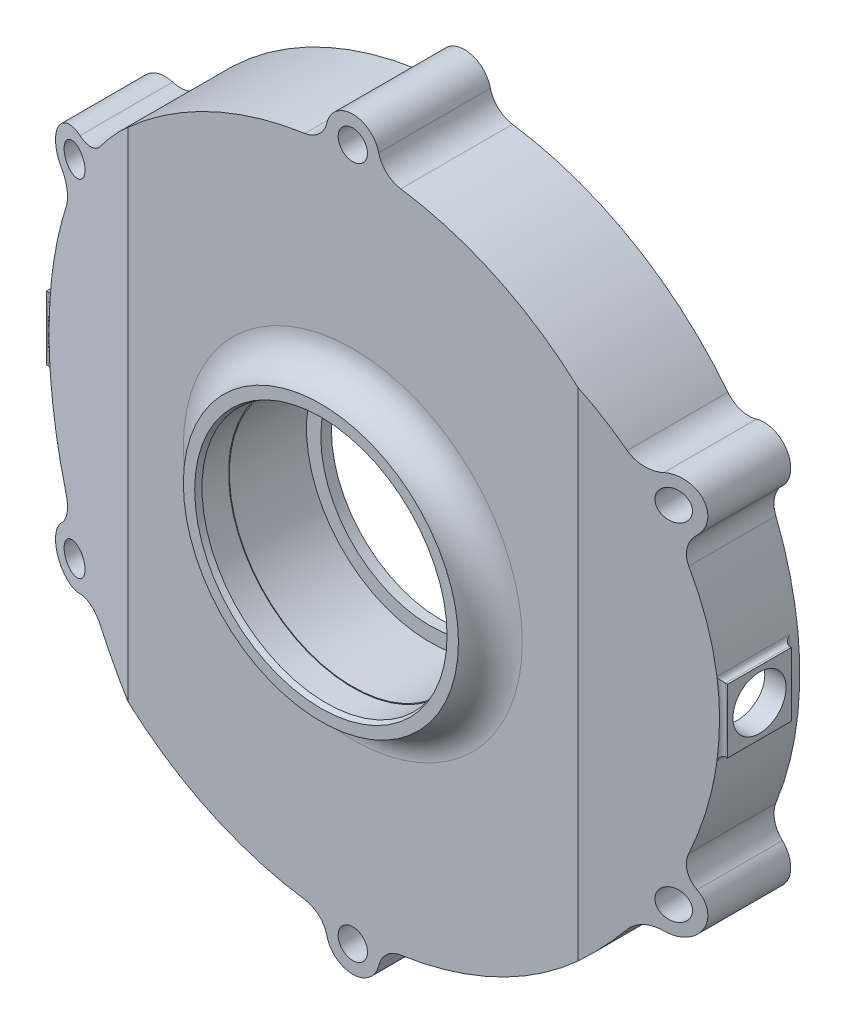
SolidWorks part; units mm, degrees
material "7075-T6 (SN)"
ref_plane "Front Plane" through (0, 0, 0) normal (0, 0, 1) x (1, 0, 0)
ref_plane "Top Plane" through (0, 0, 0) normal (0, 1, 0) x (1, 0, 0)
ref_plane "Right Plane" through (0, 0, 0) normal (1, 0, 0) x (0, 0, -1)
sketch "Sketch2" plane through (0, 0, 0) normal (1, 0, 0) x (0, 0, -1)
  line L0 (-66.5, 0) -> (66.5, 0) construction
  line L1 (0.1604, 63) -> (-20.8396, 63)
  line L3 (0.1604, 60) -> (-18.6396, 60)
  line L5 (0.1604, 63) -> (0.1604, 60)
  line L8 (-6.3396, 23.2) -> (-6.3396, 20.5148)
  line L11 (-6.3396, 20.5148) -> (-4.3396, 20.5148)
  line L14 (-18.8396, 59.8) -> (-18.8396, 27.5)
  line L21 (-20.8396, 23.2) -> (-6.3396, 23.2)
  line L22 (-20.8396, 23.2) -> (-20.8396, 63)
  line L25 (-4.3396, 27.136) -> (-4.3396, 20.5148)
  line L26 (-18.8396, 27.5) -> (-5.3396, 27.5)
  line L27 (-5.3396, 27.5) -> (-4.3396, 27.136)
  arc A0 (-18.6396, 60) -> (-18.8396, 59.8) centre (-18.6396, 59.8) ccw
  point P4 (0, 0)
  point P9 (-4.3396, 27.5)
  point P22 (-20.8396, 23.2)
  dimension "D8" = 0.2
  dimension "D12" = 20
  dimension "D4" = 1
  dimension "D2" = 27.5
  dimension "D3" = 3
  dimension "D5" = 21
  dimension "D6" = 2
  dimension "D7" = 14.5
  dimension "D9" = 2.6852
  dimension "D10" = 2
  dimension "D11" = 4.3
revolve "Revolve1" add sketch "Sketch2" angle 360 about L0
sketch "Sketch4" plane through (0, 0, -0.1604) normal (0, 0, -1) x (-1, 0, 0)
  line L0 (0, 0) -> (0, 65) construction
  circle A0 centre (0, 65) radius 5
  circle A2 centre (0, 65) radius 3
  dimension "D1" = 6
  dimension "D4" = 10
  dimension "D2" = 65
extrude "Boss-Extrude3" add sketch "Sketch4" along direction (0, 0, 1) on the side against the normal through all contours A0
sketch "Sketch11" plane through (0, 0, -0.1604) normal (0, 0, -1) x (-1, 0, 0)
  circle A0 centre (56.2917, 32.5) radius 2.75
  circle A1 centre (0, 65) radius 2.75
  circle A2 centre (56.2917, -32.5) radius 2.75
  circle A3 centre (0, -65) radius 2.75
  circle A4 centre (-56.2917, -32.5) radius 2.75
  circle A5 centre (-56.2917, 32.5) radius 2.75
  point P15 (0, 0)
  dimension "D1" = 5.5
  dimension "D2" = 65
  dimension "D3" = 6
fillet "Fillet2" radius 5 2 edges at (-4.5086, 62.8385, 10.3396) (4.5086, 62.8385, 10.3396)
pattern_circular "CirPattern2" count 6 over 360 about axis through (0, 0, -0.1604) along (0, 0, 1) of "Boss-Extrude3", "Fillet2"
chamfer "Chamfer1" distance 0.5 angle 45 1 edges at (60, 0, -0.1604)
sketch "Sketch20" plane through (0, 0, 0) normal (0, 1, 0) x (1, 0, 0)
  line L0 (-63, -12.8396) -> (-35, -20.8396)
  line L1 (-63, 0.1604) -> (-63, -20.8396) construction
  line L3 (-35, -20.8396) -> (-63, -20.8396)
  line L4 (-63, -20.8396) -> (-63, -12.8396)
  line L5 (0, -20.8396) -> (0, 8.0819) construction
  line L6 (-4.866, -20.8396) -> (4.866, -20.8396) construction
  line L7 (63, -20.8396) -> (63, -12.8396)
  line L8 (35, -20.8396) -> (63, -20.8396)
  line L9 (63, -12.8396) -> (35, -20.8396)
  dimension "D1" = 28
  dimension "D2" = 8
extrude "Cut-Extrude15" cut sketch "Sketch20" against normal blind 60 and the other way blind 60 contours L7 L9 L8 | L0 L3 L4 region at (53.6667, 0, 18.173)
sketch "Sketch21" plane through (0, 0, 0) normal (0, 1, 0) x (1, 0, 0)
  line L0 (-63, -12.8396) -> (-35, -20.8396)
  line L1 (-35, -20.8396) -> (-42.2801, -20.8396)
  line L2 (-42.2801, -20.8396) -> (-63, -14.9197)
  line L3 (-63, -12.8396) -> (-63, -14.9197)
  line L4 (0, -20.8396) -> (0, -12.247) construction
  line L5 (-4.866, -20.8396) -> (4.866, -20.8396) construction
  line L6 (63, -12.8396) -> (63, -14.9197)
  line L7 (42.2801, -20.8396) -> (63, -14.9197)
  line L8 (35, -20.8396) -> (42.2801, -20.8396)
  line L9 (63, -12.8396) -> (35, -20.8396)
  dimension "D1" = 2
extrude "Boss-Extrude8" add sketch "Sketch21" along normal blind 60 and the other way blind 60
sketch "Sketch22" plane through (0, 0, -0.1604) normal (0, 0, -1) x (-1, 0, 0)
  line L0 (35, 52.3832) -> (35, 60)
  line L3 (63, -60) -> (35, -60)
  line L4 (35, -60) -> (35, -52.3832)
  line L5 (63, 60) -> (35, 60)
  line L6 (63, -60) -> (63, 60)
  line L7 (-35, 52.3832) -> (-35, 60)
  line L8 (-35, 60) -> (-63, 60)
  line L9 (-63, 60) -> (-63, -60)
  line L10 (-63, -60) -> (-35, -60)
  line L11 (-35, -60) -> (-35, -52.3832)
  arc A24 (-9.0163, 62.3515) -> (-49.4898, 38.9841) centre (0, 0) ccw
  arc A25 (-54.8546, 37.289) -> (-49.4898, 38.9841) centre (-53.4176, 42.0781) ccw
  arc A26 (-54.8546, 37.289) -> (-59.7206, 28.861) centre (-56.2917, 32.5) ccw
  arc A27 (-58.5061, 23.3674) -> (-59.7206, 28.861) centre (-63.1495, 25.2219) ccw
  arc A28 (-58.5061, 23.3674) -> (-58.5061, -23.3674) centre (0, 0) ccw
  arc A29 (-59.7206, -28.861) -> (-58.5061, -23.3674) centre (-63.1495, -25.2219) ccw
  arc A30 (-59.7206, -28.861) -> (-54.8546, -37.289) centre (-56.2917, -32.5) ccw
  arc A31 (-49.4898, -38.9841) -> (-54.8546, -37.289) centre (-53.4176, -42.0781) ccw
  arc A32 (-49.4898, -38.9841) -> (-9.0163, -62.3515) centre (0, 0) ccw
  arc A33 (-4.866, -66.15) -> (-9.0163, -62.3515) centre (-9.7319, -67.3) ccw
  arc A34 (-4.866, -66.15) -> (4.866, -66.15) centre (0, -65) ccw
  arc A35 (9.0163, -62.3515) -> (4.866, -66.15) centre (9.7319, -67.3) ccw
  arc A36 (9.0163, -62.3515) -> (49.4898, -38.9841) centre (0, 0) ccw
  arc A44 (54.8546, -37.289) -> (49.4898, -38.9841) centre (53.4176, -42.0781) ccw
  arc A45 (54.8546, -37.289) -> (59.7206, -28.861) centre (56.2917, -32.5) ccw
  arc A46 (58.5061, -23.3674) -> (59.7206, -28.861) centre (63.1495, -25.2219) ccw
  arc A47 (58.5061, -23.3674) -> (58.5061, 23.3674) centre (0, 0) ccw
  arc A69 (59.7206, 28.861) -> (58.5061, 23.3674) centre (63.1495, 25.2219) ccw
  arc A70 (59.7206, 28.861) -> (54.8546, 37.289) centre (56.2917, 32.5) ccw
  arc A71 (49.4898, 38.9841) -> (54.8546, 37.289) centre (53.4176, 42.0781) ccw
  arc A72 (49.4898, 38.9841) -> (9.0163, 62.3515) centre (0, 0) ccw
  arc A73 (4.866, 66.15) -> (9.0163, 62.3515) centre (9.7319, 67.3) ccw
  arc A74 (4.866, 66.15) -> (-4.866, 66.15) centre (0, 65) ccw
  arc A75 (-9.0163, 62.3515) -> (-4.866, 66.15) centre (-9.7319, 67.3) ccw
  arc A76 (-35, 52.3832) -> (-49.4898, 38.9841) centre (0, 0) ccw
  arc A77 (-54.8546, 37.289) -> (-49.4898, 38.9841) centre (-53.4176, 42.0781) ccw
  arc A78 (-54.8546, 37.289) -> (-59.7206, 28.861) centre (-56.2917, 32.5) ccw
  arc A79 (-58.5061, 23.3674) -> (-59.7206, 28.861) centre (-63.1495, 25.2219) ccw
  arc A80 (-58.5061, 23.3674) -> (-58.5061, -23.3674) centre (0, 0) ccw
  arc A81 (-59.7206, -28.861) -> (-58.5061, -23.3674) centre (-63.1495, -25.2219) ccw
  arc A82 (-59.7206, -28.861) -> (-54.8546, -37.289) centre (-56.2917, -32.5) ccw
  arc A83 (-49.4898, -38.9841) -> (-54.8546, -37.289) centre (-53.4176, -42.0781) ccw
  arc A84 (-49.4898, -38.9841) -> (-35, -52.3832) centre (0, 0) ccw
  arc A88 (35, -52.3832) -> (49.4898, -38.9841) centre (0, 0) ccw
  arc A89 (54.8546, -37.289) -> (49.4898, -38.9841) centre (53.4176, -42.0781) ccw
  arc A90 (54.8546, -37.289) -> (59.7206, -28.861) centre (56.2917, -32.5) ccw
  arc A91 (58.5061, -23.3674) -> (59.7206, -28.861) centre (63.1495, -25.2219) ccw
  arc A92 (58.5061, -23.3674) -> (58.5061, 23.3674) centre (0, 0) ccw
  arc A93 (59.7206, 28.861) -> (58.5061, 23.3674) centre (63.1495, 25.2219) ccw
  arc A94 (59.7206, 28.861) -> (54.8546, 37.289) centre (56.2917, 32.5) ccw
  arc A95 (49.4898, 38.9841) -> (54.8546, 37.289) centre (53.4176, 42.0781) ccw
  arc A96 (49.4898, 38.9841) -> (35, 52.3832) centre (0, 0) ccw
  arc M31 (-9.0163, 62.3515) -> (-49.4898, 38.9841) centre (0, 0) ccw
  arc M32 (-49.4898, 38.9841) -> (-54.8546, 37.289) centre (-53.4176, 42.0781) cw
  arc M33 (-54.8546, 37.289) -> (-59.7206, 28.861) centre (-56.2917, 32.5) ccw
  arc M34 (-59.7206, 28.861) -> (-58.5061, 23.3674) centre (-63.1495, 25.2219) cw
  arc M35 (-58.5061, 23.3674) -> (-58.5061, -23.3674) centre (0, 0) ccw
  arc M36 (-58.5061, -23.3674) -> (-59.7206, -28.861) centre (-63.1495, -25.2219) cw
  arc M37 (-59.7206, -28.861) -> (-54.8546, -37.289) centre (-56.2917, -32.5) ccw
  arc M38 (-54.8546, -37.289) -> (-49.4898, -38.9841) centre (-53.4176, -42.0781) cw
  arc M39 (-49.4898, -38.9841) -> (-9.0163, -62.3515) centre (0, 0) ccw
  arc M43 (9.0163, -62.3515) -> (49.4898, -38.9841) centre (0, 0) ccw
  arc M44 (49.4898, -38.9841) -> (54.8546, -37.289) centre (53.4176, -42.0781) cw
  arc M45 (54.8546, -37.289) -> (59.7206, -28.861) centre (56.2917, -32.5) ccw
  arc M46 (59.7206, -28.861) -> (58.5061, -23.3674) centre (63.1495, -25.2219) cw
  arc M47 (58.5061, -23.3674) -> (58.5061, 23.3674) centre (0, 0) ccw
  arc M48 (58.5061, 23.3674) -> (59.7206, 28.861) centre (63.1495, 25.2219) cw
  arc M49 (59.7206, 28.861) -> (54.8546, 37.289) centre (56.2917, 32.5) ccw
  arc M50 (54.8546, 37.289) -> (49.4898, 38.9841) centre (53.4176, 42.0781) cw
  arc M51 (49.4898, 38.9841) -> (9.0163, 62.3515) centre (0, 0) ccw
  dimension "D1" = 0
extrude "Cut-Extrude16" cut sketch "Sketch22" against normal blind 25 contours L6 L5 L0 M47 M51 M50 M49 M48 | L3 L6 L4 M47 M46 M45 M44 M43 | L8 L9 L7 M35 M34 M33 M32 M31 | L10 L11 L9 M39 M38 M37 M36 M35 region at (-52.6197, 46.6934, -0.1604) region at (-52.6197, -46.6934, -0.1604) region at (52.6197, 46.6934, -0.1604) region at (52.6197, -46.6934, -0.1604)
ref_plane "Plane1" through (-64, 0, 0) normal (1, 0, 0) x (0, 0, -1)
sketch "Sketch23" plane through (-64, 0, 0) normal (1, 0, 0) x (0, 0, -1)
  line L1 (-2.4197, -6) -> (-14.4197, -6)
  line L2 (-2.4197, -6) -> (-2.4197, 6)
  line L3 (-2.4197, 6) -> (-14.4197, 6)
  line L4 (-14.4197, -6) -> (-14.4197, 6)
  line L5 (-2.4197, -6) -> (-14.4197, 6) construction
  line L6 (-2.4197, 6) -> (-14.4197, -6) construction
  circle A0 centre (-8.4197, 0) radius 5
  ellipse E0 centre (-32.9197, 0) end of major axis (-32.9197, 63) minor radius 18 (-16.2036, -23.3674) -> (-16.2036, 23.3674) ccw construction
  point P0 (-8.4197, 0)
  point P5 (-14.9197, 0)
  dimension "D5" = 10
  dimension "D1" = 12
  dimension "D2" = 12
  dimension "D3" = 6.5
  dimension "D4" = 0
extrude "Boss-Extrude9" add sketch "Sketch23" along normal blind 2.5
sketch "Sketch24" plane through (-64, 0, 0) normal (-1, 0, 0) x (0, 0, 1)
  circle A0 centre (8.4197, 0) radius 5
extrude "Cut-Extrude17" cut sketch "Sketch24" against normal blind 10
mirror "Mirror3" about plane through (0, 0, 0) normal (1, 0, 0) of "Boss-Extrude9"
sketch "Sketch25" plane through (64, 0, 0) normal (1, 0, 0) x (0, 0, -1)
  circle A0 centre (-8.4197, 0) radius 5
extrude "Cut-Extrude18" cut sketch "Sketch25" against normal blind 5
fillet "Fillet5" radius 1 8 edges at (-62.7136, 6, 8.4197) (-63, 0, 2.4197) (-62.7136, -6, 8.4197) (63, 0, 2.4197) (62.7136, 6, 8.4197) (62.7136, -6, 8.4197) (63, 0, 14.4197) (-63, 0, 14.4197)
sketch "Sketch28" plane through (0, 0, 20.8396) normal (0, 0, 1) x (1, 0, 0)
  circle A0 centre (0, 0) radius 23.35
  circle A1 centre (0, 0) radius 25.85
  dimension "D1" = 2.5
extrude "Boss-Extrude12" add sketch "Sketch28" along normal blind 6
fillet "Fillet9" radius 6 1 edges at (-25.85, 0, 20.8396)
chamfer "Chamfer2" distance 1 angle 20 1 edges at (23.35, 0, 26.8396) first distance on face at (23.35, 0, 26.8396)
extrude "Cut-Extrude19" cut sketch "Sketch11" against normal through all
sketch "Sketch29" plane through (0, 0, 18.8396) normal (0, 0, -1) x (-1, 0, 0)
  circle A0 centre (0, 0) radius 27.136
  circle A1 centre (0, 0) radius 31.136
  dimension "D1" = 4
extrude "Boss-Extrude13" add sketch "Sketch29" along normal blind 1
fillet "Fillet10" radius 0.2 3 edges at (-31.136, 0, 17.8396) (31.136, 0, 18.8396) (-27.5, 0, 17.8396)
